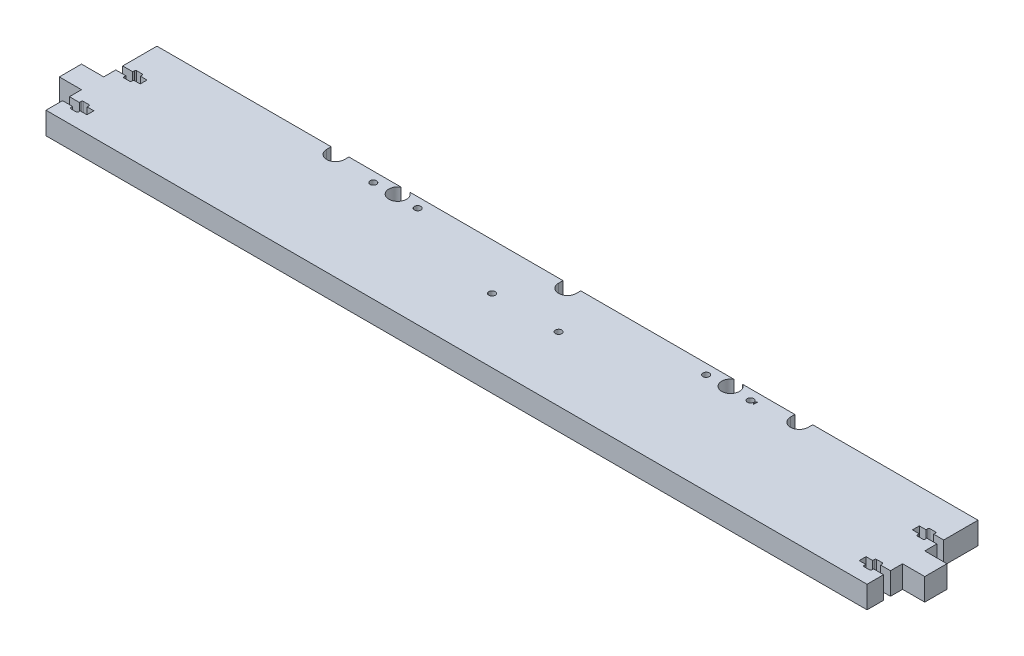
SolidWorks part; units mm, degrees
ref_plane "Front Plane" through (0, 0, 0) normal (0, 0, 1) x (1, 0, 0)
ref_plane "Top Plane" through (0, 0, 0) normal (0, 1, 0) x (1, 0, 0)
ref_plane "Right Plane" through (0, 0, 0) normal (1, 0, 0) x (0, 0, -1)
sketch "Sketch1" plane through (0, 0, 0) normal (0, 1, 0) x (1, 0, 0)
  line L0 (0, 25) -> (0, -25)
  line L1 (-185, 25) -> (0, 25)
  line L2 (-185, 25) -> (-185, -25) construction
  line L3 (-185, -25) -> (0, -25)
  line L4 (-185, -4) -> (-195, -4) construction
  line L5 (-185, 25) -> (0, 0) construction
  line L6 (-185, -25) -> (0, 0) construction
  line L7 (-185, -9) -> (-195, -9)
  line L8 (-195, -9) -> (-195, 1)
  line L9 (-195, 1) -> (-185, 1)
  line L10 (-185, 1) -> (-185, 25)
  line L11 (-185, -9) -> (-185, -25)
  line L47 (0, -25) -> (0, 25) construction
  line L89 (0, -25) -> (0, 25) construction
  point P0 (0, 0)
  dimension "D1" = 185
  dimension "D25" = 25
  dimension "D4" = 50
  dimension "D3" = 21
  dimension "D5" = 10
  dimension "D6" = 10
  dimension "D7" = 5
extrude "MainBody" add sketch "Sketch1" along normal blind 10 contours L3 region at (-93.5428, 0, 0.0428)
sketch "Sketch5" plane through (0, 10, 0) normal (0, 1, 0) x (1, 0, 0)
  line L0 (-185, 8) -> (-174, 8) construction
  line L1 (-185, 1) -> (-185, 25) construction
  line L2 (-185, 9.55) -> (-174, 9.55) construction
  line L3 (-174, 9.55) -> (-174, 6.45) construction
  line L4 (-174, 6.45) -> (-185, 6.45) construction
  line L5 (-185, 9.55) -> (-180.5, 9.55)
  line L6 (-180.5, 9.55) -> (-180.5, 10.35)
  line L7 (-180, 10.85) -> (-177.5, 10.85)
  line L8 (-177, 10.35) -> (-177, 9.55)
  line L9 (-177, 9.55) -> (-174, 9.55)
  line L10 (-174, 9.55) -> (-174, 6.45)
  line L11 (-185, 6.45) -> (-185, 9.55)
  line L12 (-195, -9) -> (-195, 1) construction
  line L13 (-185, 6.45) -> (-174, 6.45) construction
  line L14 (-177, 6.45) -> (-174, 6.45)
  line L15 (-177, 5.65) -> (-177, 6.45)
  line L16 (-180, 5.15) -> (-177.5, 5.15)
  line L17 (-180.5, 6.45) -> (-180.5, 5.65)
  line L18 (-185, 6.45) -> (-180.5, 6.45)
  line L19 (-185, 1) -> (-185, -9) construction
  line L20 (-195, -4) -> (-185, -4) construction
  line L21 (-195, -9) -> (-195, 1) construction
  line L22 (-185, -14.45) -> (-174, -14.45) construction
  line L23 (-174, -14.45) -> (-185, -14.45) construction
  line L24 (-174, -17.55) -> (-174, -14.45) construction
  line L25 (-185, -17.55) -> (-174, -17.55) construction
  line L26 (-185, -16) -> (-174, -16) construction
  line L27 (-185, -14.45) -> (-180.5, -14.45)
  line L28 (-180.5, -14.45) -> (-180.5, -13.65)
  line L29 (-180, -13.15) -> (-177.5, -13.15)
  line L30 (-177, -13.65) -> (-177, -14.45)
  line L31 (-177, -14.45) -> (-174, -14.45)
  line L32 (-185, -14.45) -> (-185, -17.55)
  line L33 (-174, -17.55) -> (-174, -14.45)
  line L34 (-177, -17.55) -> (-174, -17.55)
  line L35 (-177, -18.35) -> (-177, -17.55)
  line L36 (-180, -18.85) -> (-177.5, -18.85)
  line L37 (-180.5, -17.55) -> (-180.5, -18.35)
  line L38 (-185, -17.55) -> (-180.5, -17.55)
  line L39 (-185, 6.45) -> (-174, 6.45) construction
  arc A0 (-177.5, 10.85) -> (-177, 10.35) centre (-177.5, 10.35) cw
  arc A1 (-180.5, 10.35) -> (-180, 10.85) centre (-180, 10.35) cw
  arc A2 (-180.5, 5.65) -> (-180, 5.15) centre (-180, 5.65) ccw
  arc A3 (-177.5, 5.15) -> (-177, 5.65) centre (-177.5, 5.65) ccw
  arc A4 (-177.5, -13.15) -> (-177, -13.65) centre (-177.5, -13.65) cw
  arc A5 (-180.5, -13.65) -> (-180, -13.15) centre (-180, -13.65) cw
  arc A6 (-180.5, -18.35) -> (-180, -18.85) centre (-180, -18.35) ccw
  arc A7 (-177.5, -18.85) -> (-177, -18.35) centre (-177.5, -18.35) ccw
  point P6 (-195, -4)
  point P17 (-177, 10.85)
  point P20 (-180.5, 10.85)
  point P29 (-180.5, 5.15)
  point P30 (-177, 5.15)
  point P61 (-177, -13.15)
  point P62 (-180.5, -13.15)
  point P63 (-180.5, -18.85)
  point P64 (-177, -18.85)
  dimension "D8" = 0.5
  dimension "D1" = 11
  dimension "D2" = 1.55
  dimension "D4" = 3.5
  dimension "D5" = 8
  dimension "D6" = 2.85
  dimension "D7" = 12
extrude "ScrewCutouts" cut sketch "Sketch5" against normal through all
mirror "Mirror1" about plane through (0, 0, 0) normal (1, 0, 0) of "ScrewCutouts", "MainBody"
sketch "Sketch3" plane through (0, 10, 0) normal (0, 1, 0) x (1, 0, 0)
  line L0 (2, 25) -> (2, -25) construction
  line L1 (-185, 25) -> (185, 25) construction
  line L2 (-185, -25) -> (185, -25) construction
  line L3 (-63, 20.5) -> (-83, 20.5) construction
  line L4 (-73, 17.5) -> (-73, 25.5) construction
  line L5 (77, 17.5) -> (77, 25.5) construction
  line L6 (67, 20.5) -> (87, 20.5) construction
  circle A0 centre (-73, 21.5) radius 4
  circle A1 centre (-83, 20.5) radius 1.45
  circle A2 centre (-63, 20.5) radius 1.45
  circle A3 centre (67, 20.5) radius 1.45
  circle A4 centre (87, 20.5) radius 1.45
  circle A5 centre (77, 21.5) radius 4
  dimension "D2" = 8
  dimension "D4" = 2.9
  dimension "D1" = 3.5
  dimension "D5" = 75
  dimension "D6" = 2
  dimension "D3" = 10
  dimension "D7" = 1
extrude "RodCutouts" cut sketch "Sketch3" against normal through all
sketch "Sketch6" plane through (0, 10, 0) normal (0, 1, 0) x (1, 0, 0)
  line L0 (-73, 21.5) -> (77, 21.5) construction
  line L1 (2, 21.5) -> (2, -25) construction
  line L2 (-185, -25) -> (185, -25) construction
  line L3 (17, 4) -> (-13, 4) construction
  line L4 (-71.0635, 25) -> (75.0635, 25) construction
  circle A0 centre (-13, 4) radius 1.45
  circle A1 centre (17, 4) radius 1.45
  point P13 (2, 4)
  dimension "D3" = 21
  dimension "D1" = 2.9
  dimension "D2" = 15
extrude "Cut-Extrude1" cut sketch "Sketch6" against normal through all
sketch "Sketch7" plane through (0, 10, 0) normal (0, 1, 0) x (1, 0, 0)
  line L0 (-73, 21.5) -> (77, 21.5) construction
  line L1 (2, 21.5) -> (2, -25) construction
  line L3 (-102.5, 25) -> (-102.5, 23) construction
  line L4 (-185, 25) -> (-74.9365, 25) construction
  line L5 (-98.5, 25) -> (-98.5, 23)
  line L6 (-106.5, 25) -> (-106.5, 23)
  line L7 (106.5, 25) -> (106.5, 23) construction
  line L8 (102.5, 25) -> (102.5, 23)
  line L9 (110.5, 25) -> (110.5, 23)
  line L12 (-185, -25) -> (185, -25) construction
  arc A0 (-98.5, 25) -> (-106.5, 25) centre (-102.5, 25) ccw
  arc A1 (-106.5, 23) -> (-98.5, 23) centre (-102.5, 23) ccw
  arc A2 (102.5, 25) -> (110.5, 25) centre (106.5, 25) cw
  arc A3 (110.5, 23) -> (102.5, 23) centre (106.5, 23) cw
  point P12 (-102.5, 24)
  point P19 (106.5, 24)
  dimension "D1" = 4
  dimension "D2" = 2
  dimension "D3" = 104.5
extrude "BedAdjustmentScrewCutout" cut sketch "Sketch7" against normal through all
sketch "Sketch8" plane through (0, 10, 0) normal (0, 1, 0) x (1, 0, 0)
  line L0 (88.25, 20.5) -> (89.25, 20.5) construction
  line L1 (88.45, 20.5) -> (88.45, 25) construction
  line L2 (88.25, 20.5) -> (89.25, 21.5)
  line L3 (89.25, 21.5) -> (89.25, 19.5)
  line L4 (88.25, 20.5) -> (89.25, 19.5)
  line L5 (78.9365, 25) -> (102.5, 25) construction
  circle A1 centre (87, 20.5) radius 1.45 construction
  point P9 (89.25, 20.5)
  dimension "D1" = 1
  dimension "D2" = 1
  dimension "D3" = 0.2
extrude "DirectionKey" cut sketch "Sketch8" against normal through all
sketch "Sketch9" plane through (0, 10, 0) normal (0, 1, 0) x (1, 0, 0)
  line L0 (-13, 4) -> (17, 4) construction
  line L1 (2, 4) -> (2, 25) construction
  line L2 (-71.0635, 25) -> (75.0635, 25) construction
  line L3 (2, 27) -> (2, 23) construction
  line L4 (6, 27) -> (6, 23)
  line L5 (-2, 27) -> (-2, 23)
  arc A0 (6, 27) -> (-2, 27) centre (2, 27) ccw
  arc A1 (-2, 23) -> (6, 23) centre (2, 23) ccw
  point P10 (2, 25)
  dimension "D1" = 4
  dimension "D2" = 2
extrude "Cut-Extrude2" cut sketch "Sketch9" against normal through all
equation "\"Y-ROD-SPACING\"=75"
equation "\"Y-BED-OFFSET\"=2"
equation "\"T-SLOT-NUT-FILLET-RADIUS\"=0.5"
equation "\"T-SLOT-SCREW-SHAFT-RADIUS\"=1.55"
equation "\"T-SLOT-SCREW-SHAFT-CUTOUT-LENGTH\"=11.0"
equation "\"T-SLOT-NUT-DEPTH\"=3.5"
equation "\"T-SLOT-NUT-WIDTH\"=2.85"
equation "\"T-SLOT-NUT-END-DISTANCE\"=8"
equation "\"ACRYLIC-TAB-CUTOUT-SIZE\"=\"ACRYLIC-THICKNESS\"+\"ACRYLIC-TAB-TOLERANCE\"*2"
equation "\"ACRYLIC-M3-HOLE\"=2.9"
equation "\"D1@Sketch5\"=\"T-SLOT-SCREW-SHAFT-CUTOUT-LENGTH\""
equation "\"D2@Sketch5\"=\"T-SLOT-SCREW-SHAFT-RADIUS\""
equation "\"D4@Sketch5\"=\"T-SLOT-NUT-DEPTH\""
equation "\"D5@Sketch5\"=\"T-SLOT-NUT-END-DISTANCE\""
equation "\"D6@Sketch5\"=\"T-SLOT-NUT-WIDTH\""
equation "\"D8@Sketch5\"=\"T-SLOT-NUT-FILLET-RADIUS\""
equation "\"D4@Sketch3\"=\"ACRYLIC-M3-HOLE\""
equation "\"D5@Sketch3\"=\"Y-ROD-SPACING\""
equation "\"D6@Sketch3\"=\"Y-BED-OFFSET\""
equation "\"Y-BED-ROD-INSET\"=3.5"
equation "\"D1@Sketch3\"=\"Y-BED-ROD-INSET\""
equation "\"SMOOTHROD-CAP-SCREW-DISTANCE\"=20"
equation "\"D3@Sketch3\"=\"SMOOTHROD-CAP-SCREW-DISTANCE\"/2"
equation "\"ACRYLIC-TAB-WIDTH\"=\"ACRYLIC-THICKNESS\""
equation "\"FRAME-WIDTH-INNER\"=370"
equation "\"D6@Sketch1\"=\"ACRYLIC-TAB-WIDTH\""
equation "\"D5@Sketch1\"=\"ACRYLIC-TAB-WIDTH\""
equation "\"D1@Sketch1\"=\"FRAME-WIDTH-INNER\"/2"
equation "\"X-ROD-SPACING\"=45"
equation "\"Z-ROD-SPACING\"=17.5"
equation "\"ACRYLIC-THICKNESS\"=10"
equation "\"ACRYLIC-THICKNESS2\"=4.5"
equation "\"NEMA17-HOLE-SPACING\"=31"
equation "\"NEMA17-CENTRAL-CUTOUT\"=22.5"
equation "\"Z-BRACKET-REACH\"=55"
equation "\"TOP-BRACKET-SPACING\"=40"
equation "\"SMOOTHROD-X-LENGTH\"=350"
equation "\"SMOOTHROD-Y-LENGTH\"=350"
equation "\"SMOOTHROD-Z-LENGTH\"=350"
equation "\"SMOOTHROD-TIGHTENING-HEADROOM\"=.25"
equation "\"LEADSCREW-Z-LENGTH\"=300"
equation "\"SCREW-LENGTH-FRAME\"=\"ACRYLIC-THICKNESS\" + 10"
equation "\"SCREW-HEAD-RADIUS\"=6"
equation "\"PRINTED-X-SMOOTHROD-DIAMETER\"=8.4"
equation "\"PRINTED-X-SMOOTHROD-CUTOUT\"=10"
equation "\"PRINTED-X-BASE-HEIGHT\"=10"
equation "\"PRINTED-LM8UU-CUTOUT-SIZE\"=15.5"
equation "\"PRINTED-LM8UU-CUTOUT-LENGTH\"=24.5"
equation "\"PRINTED-X-IDLER-HEIGHT\"=16"
equation "\"PSU-MOUNTING-WIDTH\"=95"
equation "\"PSU-MOUNTING-HEIGHT\"=177"
equation "\"D1@MainBody\"=\"ACRYLIC-THICKNESS\""
equation "\"D7@Sketch1\"=\"ACRYLIC-TAB-WIDTH\"/2"
equation "\"D1@Sketch6\"=\"ACRYLIC-M3-HOLE\""
equation "\"Y-BELT-TO-ROD-DISTANCE\"=20"
equation "\"Y-BED-SCREW-SPACING\"=209"
equation "\"Z-ROD-INSET\"=16"
equation "\"SPOOL-HOLDER-ROD-SPACING\"=150"
equation "\"D3@Sketch7\"=\"Y-BED-SCREW-SPACING\"/2"
equation "\"Y-BED-SCREW-CUTOUT-SLOT-HEIGHT\"=2"
equation "\"D2@Sketch7\"=\"Y-BED-SCREW-CUTOUT-SLOT-HEIGHT\""
equation "\"ACRYLIC-TAB-TOLERANCE\"=-.05"
equation "\"SCREW-LENGTH-MOTOR\"=\"ACRYLIC-THICKNESS\" + 5"
equation "\"SCREW-LENGTH-EXTRUDER\"=28"
equation "\"PRINTED-M3-HOLE\"=3.5"
equation "\"ACRYLIC-X-CARRIAGE-WIDTH\"=55"
equation "\"ACRYLIC-X-CARRIAGE-HEIGHT\"=75"
equation "\"ACRYLIC-X-CARRIAGE-LM8UU-CUTOUT-WIDTH\"=24.25"
equation "\"ACRYLIC-X-CARRIAGE-LM8UU-CUTOUT-HEIGHT\"=11.0"
equation "\"ACRYLIC-X-CARRIAGE-SCREW-SPACING-X\"=15"
equation "\"ACRYLIC-X-CARRIAGE-SCREW-SPACING-Y\"=33"
equation "\"ACRYLIC-X-CARRIAGE-CENTER-TAB-SPACING\"=14"
equation "\"ACRYLIC-X-CARRIAGE-EXTRUDER-OFFSET\"=26"
equation "\"ACRYLIC-X-CARRIAGE-EXTRUDER-ANGLE\"=90"
equation "\"ACRYLIC-X-CARRIAGE-EXTRUDER-SHELF-DEPTH\"=\"ACRYLIC-X-CARRIAGE-EXTRUDER-OFFSET\" + 28"
equation "\"ACRYLIC-X-CARRIAGE-EXTRUDER-BRACE-SPACING\"=23"
equation "\"ACRYLIC-X-CARRIAGE-EXTRUDER-BRACE-TAB-OFFSET\"=20"
equation "\"ACRYLIC-X-CARRIAGE-EXTRUDER-BRACE-HEIGHT\"=35"
equation "\"ACRYLIC-X-CARRIAGE-EXTRUDER-BRACE-SCREW-SPACING\"=22"
equation "\"ACRYLIC-X-CARRIAGE-DUAL-WIDTH-MULTIPLIER\"=1.65"
equation "\"ACRYLIC-X-CARRIAGE-DUAL-HOTEND-SPACING\"=42"
equation "\"ACRYLIC-X-CARRIAGE-DUAL-WIDTH\"=75"
equation "\"ACRYLIC-X-CARRIAGE-DUAL-HOTEND-SEPARATION\"=36"
equation "\"ACRYLIC-X-CARRIAGE-DUAL-MOUNT-PLATE-DEPTH\"=75"
equation "\"ACRYLIC-X-CARRIAGE-DUAL-MOUNT-BRACE-WIDTH\"=33"
equation "\"ACRYLIC-X-CARRIAGE-DUAL-MOUNT-SCREW-WIDTH\"=40"
equation "\"BLOWER-FAN-WIDTH\"=15"
equation "\"D2@Sketch9\"=\"Y-BED-SCREW-CUTOUT-SLOT-HEIGHT\""
